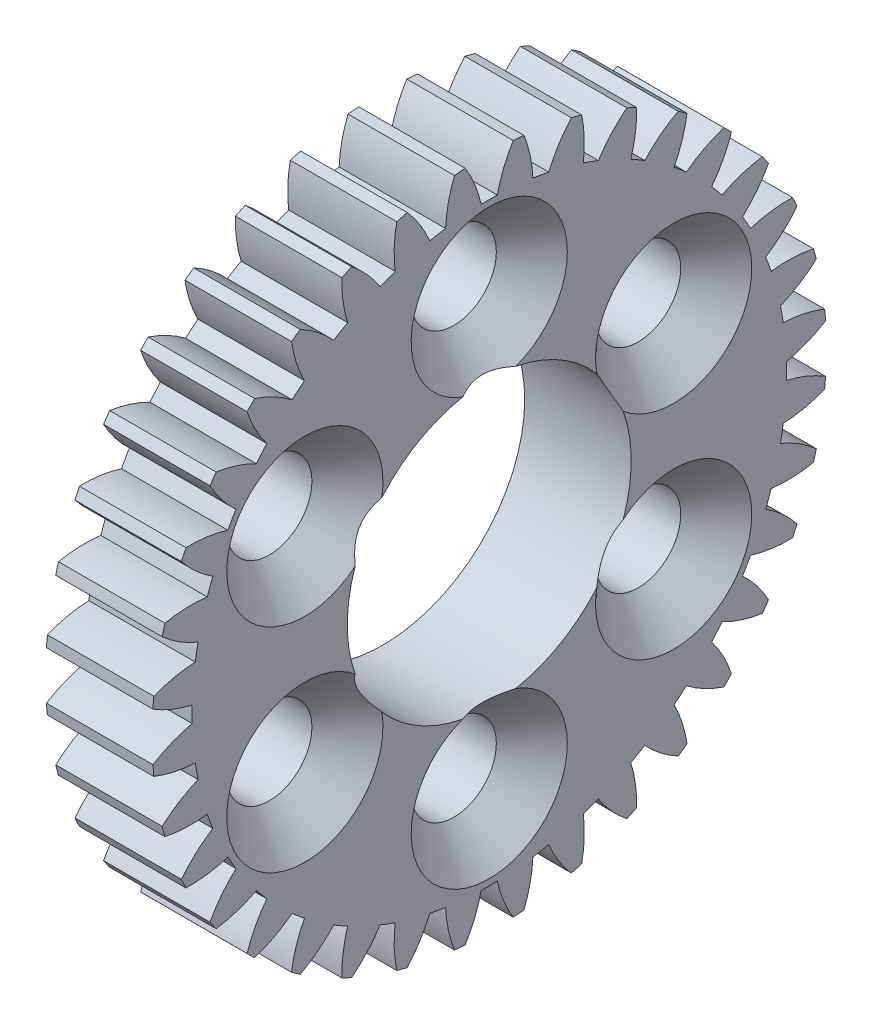
SolidWorks part; units mm, degrees
material "Náilon 101"
ref_plane "Plane1" through (0, 0, 0) normal (0, 0, 1) x (1, 0, 0)
ref_plane "Plane2" through (0, 0, 0) normal (0, 1, 0) x (1, 0, 0)
ref_plane "Plane3" through (0, 0, 0) normal (1, 0, 0) x (0, 0, -1)
sketch "HoldingSke" plane through (0, 0, 0) normal (0, 1, 0) x (1, 0, 0)
  line L0 (0, 0) -> (1.618, -1.1756)
  line L1 (-15, 0) -> (100, 0) construction
  line L2 (0, 0) -> (-2.1039, 2.3779)
  line L3 (0, 0) -> (-11.863, 4.5341)
  line L4 (0, 0) -> (6.9867, 5.0761)
  line L5 (0, 0) -> (-46.8476, -17.4728)
  line L6 (0, 0) -> (-2.4869, -1.6779)
  line L7 (-2.1039, 2.3779) -> (8.6586, 51.2059)
  line L8 (-76.2, 54.61) -> (-74.8, 54.61)
  line L9 (-71.009, 38.7566) -> (-53.1078, 45.2721)
  line L10 (-76.2, 71.12) -> (104.1128, 71.12)
  line L11 (0, 0) -> (-3, 0)
  line L12 (-76.2, 101.6) -> (-76.181, 101.6)
  line L13 (24.9733, 27.94) -> (52.9518, 28.4284)
  line L14 (24.9733, 27.94) -> (24.9743, 27.94)
  line L15 (24.9733, 27.94) -> (100.4006, 29.5858)
  line L16 (-63.627, -0.5) -> (-12.827, -0.5)
  circle A0 centre (0, 0) radius 4
  circle A1 centre (0, 0) radius 8.374
  circle A2 centre (0, 0) radius 37.5
  circle A3 centre (0, 0) radius 4
  dimension "Num_teeth" = 36
  dimension "Pitch_radius" = 180.3128
  dimension "Width" = 3
  dimension "Thickness" = 3
sketch "BasProSke" plane through (0, 0, 0) normal (0, 1, 0) x (1, 0, 0)
  line L0 (-10, 0) -> (60, 0) construction
  line L1 (0, 0) -> (0, 9.5)
  line L2 (0, 0) -> (3, 0)
  line L3 (3, 0) -> (3, 9.5)
  line L4 (3, 9.5) -> (0, 9.5)
  dimension "Thickness" = 3
  dimension "Diameter" = 19
revolve "Base-Revolve" add sketch "BasProSke" angle 360 about L0
sketch "TooCutSke" plane through (0, 0, 0) normal (1, 0, 0) x (0, 0, -1)
  line L1 (0, 0) -> (0, 107) construction
  line L2 (0, 0) -> (-0.4258, 8.9899) construction
  line L3 (0, 0) -> (-1.5676, 17.9172) construction
  line L4 (-0.4258, 8.9899) -> (-0.7838, 8.9586) construction
  arc A0 (0.2272, 8.3709) -> (-0.2272, 8.3709) centre (0, 0) ccw
  arc A1 (0.6921, 9.5002) -> (-0.6921, 9.5002) centre (0, 0) ccw
  circle A2 centre (0, 0) radius 9 construction
  circle A3 centre (0, 0) radius 8.4572 construction
  arc A4 (-0.2272, 8.3709) -> (-0.6921, 9.5002) centre (-3.7404, 7.5851) ccw
  arc A5 (0.6921, 9.5002) -> (0.2272, 8.3709) centre (3.7404, 7.5851) ccw
extrude "ToothCut" cut sketch "TooCutSke" along normal through all
fillet "Breaks" [suppressed] radius 0.01 tangent propagation no
fillet "RootFillets" [suppressed] radius 0.126
pattern_circular "TeethCuts" count 36 every 10 about axis through (-10, 0, 0) along (1, 0, 0) of "ToothCut", "RootFillets", "Breaks"
sketch "HubNeaOneSke" plane through (0, 0, 0) normal (-1, 0, 0) x (0, 0, 1)
  circle A0 centre (0, 0) radius 8.374
  dimension "Diameter" = 16.748
extrude "HubNearOne" [suppressed] add sketch "HubNeaOneSke" along normal blind 47.0001
sketch "HubNeaBotSke" plane through (0, 0, 0) normal (-1, 0, 0) x (0, 0, 1)
  circle A0 centre (0, 0) radius 8.374
  dimension "Diameter" = 16.748
extrude "HubNearBoth" [suppressed] add sketch "HubNeaBotSke" along normal blind 23.5
ref_plane "FarPln" through (3, 0, 0) normal (1, 0, 0) x (0, 0, -1)
sketch "HubFarSke" plane through (3, 0, 0) normal (1, 0, 0) x (0, 0, -1)
  circle A0 centre (0, 0) radius 8.374
  dimension "Diameter" = 16.748
extrude "HubFar" [suppressed] add sketch "HubFarSke" along normal blind 23.5
sketch "BorSke" plane through (0, 0, 0) normal (1, 0, 0) x (0, 0, -1)
  circle A0 centre (0, 0) radius 4
  dimension "Diameter" = 8
extrude "Bore" cut sketch "BorSke" along normal mid plane 100.0001
sketch "KeySke" plane through (0, 0, 0) normal (1, 0, 0) x (0, 0, -1)
  line L0 (-1.5, 0) -> (-1.5, 5.4)
  line L1 (-1.5, 5.4) -> (1.5, 5.4)
  line L2 (1.5, 5.4) -> (1.5, 0)
  line L3 (0, 0) -> (0, 34) construction
  line L4 (-1.5, 0) -> (1.5, 0)
  dimension "Width" = 3
extrude "Keyway" [suppressed] cut sketch "KeySke" along normal mid plane 100.0001
pattern_circular "Keyway2" [suppressed] count 2 every 90 about axis through (-10, 0, 0) along (1, 0, 0) reverse direction yes
sketch "Esboço1" plane through (3, 0, 0) normal (1, 0, 0) x (0, 0, -1)
  circle A0 centre (0, 0) radius 6 construction
  point P3 (0, 6)
  dimension "D1" = 12
hole_wizard "Escareado para parafuso com cabeça escareada chata de M21" positions "3DSketch2" profile "Esboço2" countersink size "M2" standard "ISO"
sketch3d "3DSketch2"
  point P0 (3, 6, 0)
sketch "Esboço2" plane through (3, 6, 0) normal (0, 1, 0) x (0, 0, -1)
  line L0 (0, 0) -> (0, 3.721)
  line L1 (0, 3.721) -> (1.2, 3)
  line L2 (1.2, 3) -> (1.2, 1)
  line L3 (1.2, 1) -> (2.2, 0)
  line L5 (2.2, 0) -> (0, 0)
  line L6 (-1.2, 1) -> (-2.2, 0) construction
  line L10 (0, 3.721) -> (-1.2, 3) construction
  line L11 (0, -6.35) -> (0, 107.95) construction
  dimension "Hole Dia." = 2.4
  dimension "Hole Depth" = 3
  dimension "Near C'Sink Dia." = 4.4
  dimension "Near C'Sink Angle" = 90
  dimension "Drill Angle" = 118
pattern_circular "PadrãoCircular1" count 6 over 360 about axis through (3, 0, 0) along (1, 0, 0) of "Escareado para parafuso com cabeça escareada chata de M21"
sketch "Esboço3" plane through (3, 0, 0) normal (1, 0, 0) x (0, 0, -1)
  line L0 (0, 0) -> (4, 0) construction
  line L1 (0, 0) -> (-4, 0) construction
  arc A0 (-3.031, -2.6102) -> (-0.7451, -3.93) centre (0, 0) ccw construction
  arc A1 (-0.7451, 3.93) -> (-3.031, 2.6102) centre (0, 0) ccw construction
equation "' \"Module@HoldingSke\" = 6.35"
equation "' \"Num_teeth@HoldingSke\" = 12"
equation "' \"Ap@HoldingSke\" =  20"
equation "' \"Ap@HoldingSke\" = 20"
equation "' \"Width@HoldingSke\" = 0.5 * 25.4"
equation "' \"Hub_dia@HoldingSke\"= 1 * 25.4"
equation "' \"Hub_dia@HoldingSke\" = 1 * 25.4"
equation "' \"Overall_len@HoldingSke\" = 1.0 * 25.4"
equation "' \"Bore@HoldingSke\" = 0.75 * 25.4"
equation "' \"T_dim@HoldingSke\" = 0.1 * 25.4"
equation "' \"Width@KeySke\" = 0.25 * 25.4"
equation "' \"Show_teeth@HoldingSke\" = 13"
equation "' \"Backlash@HoldingSke\" = 0.009 * 25.4"
equation "' \"Addendum_fac@HoldingSke\" = 1.0"
equation "' \"Dedendum_fac@HoldingSke\" = 1.25"
equation "' \"Dedendum_add@HoldingSke\" = 0.00005 * 25.4"
equation "' \"Clearance_fac@HoldingSke\" = 0.25"
equation "\"Pitch@HoldingSke\" = 1 / \"Module@HoldingSke\""
equation "\"Overcut_dia@TooCutSke\" = (\"Num_teeth@HoldingSke\" + 2 * \"Addendum_fac@HoldingSke\") / \"Pitch@HoldingSke\" + 0.002 * 25.4"
equation "\"Pitch_dia@TooCutSke\" = \"Num_teeth@HoldingSke\" / \"Pitch@HoldingSke\""
equation "\"Base_dia@TooCutSke\" = \"Num_teeth@HoldingSke\" / \"Pitch@HoldingSke\" * cos((\"Ap@HoldingSke\"  * 3.14159265 / 180))"
equation "\"Root_dia@TooCutSke\" = (\"Num_teeth@HoldingSke\" + 2) / \"Pitch@HoldingSke\" - 2 * (\"Addendum_fac@HoldingSke\" + \"Dedendum_fac@HoldingSke\") / \"Pitch@HoldingSke\" - \"Dedendum_add@HoldingSke\" * 2"
equation "\"Half_ang@TooCutSke\" = 180 / \"Num_teeth@HoldingSke\""
equation "\"Half_CT@TooCutSke\" = \"Num_teeth@HoldingSke\" / \"Pitch@HoldingSke\" * sin((3.14159265 / 2 / \"Num_teeth@HoldingSke\")) / 2 - 7 * \"Backlash@HoldingSke\" / 4"
equation "\"Flank_rad@TooCutSke\" = \"Num_teeth@HoldingSke\" / \"Pitch@HoldingSke\" / 5"
equation "\"Radius@RootFillets\" = \"Clearance_fac@HoldingSke\" / \"Pitch@HoldingSke\" + \"Dedendum_add@HoldingSke\""
equation "\"Break_rad@Breaks\" = 0.02 / \"Pitch@HoldingSke\""
equation "\"Thickness@HoldingSke\" = \"Width@HoldingSke\""
equation "\"OAL@HoldingSke\" = \"Thickness@HoldingSke\""
equation "\"MHD@HoldingSke\" = (\"Num_teeth@HoldingSke\" + 2) / \"Pitch@HoldingSke\" - 2 * (\"Addendum_fac@HoldingSke\" + \"Dedendum_fac@HoldingSke\")  / \"Pitch@HoldingSke\" - \"Dedendum_add@HoldingSke\" * 2"
equation "\"MBD@HoldingSke\" = (\"Num_teeth@HoldingSke\" + 2) / \"Pitch@HoldingSke\" - 2 * (\"Addendum_fac@HoldingSke\" + \"Dedendum_fac@HoldingSke\")  / \"Pitch@HoldingSke\" - \"Dedendum_add@HoldingSke\" * 2 - 0.002 * 25.4"
equation "\"MHD@HoldingSke\" = ((sgn( \"MHD@HoldingSke\" - \"Hub_dia@HoldingSke\" )-1)*( \"MHD@HoldingSke\" - \"Hub_dia@HoldingSke\" ))/-2+ \"Hub_dia@HoldingSke\""
equation "\"MBD@HoldingSke\" = ((sgn( \"MBD@HoldingSke\" - \"Bore@HoldingSke\" )-1)*( \"MBD@HoldingSke\" - \"Bore@HoldingSke\" ))/-2+ \"Bore@HoldingSke\""
equation "\"OAL@HoldingSke\" = ((sgn( \"OAL@HoldingSke\" - \"Overall_len@HoldingSke\" )+1)*( \"OAL@HoldingSke\" - \"Overall_len@HoldingSke\" ))/2 + \"Overall_len@HoldingSke\" + 0.000002 * 25.4"
equation "\"Num_teeth@TeethCuts\" = int( \"Show_teeth@HoldingSke\" ) + 1"
equation "\"Num_teeth@TeethCuts\" = ((sgn( \"Num_teeth@TeethCuts\" - \"Num_teeth@HoldingSke\" )-1)*( \"Num_teeth@TeethCuts\" - \"Num_teeth@HoldingSke\" ))/-2+ \"Num_teeth@HoldingSke\""
equation "\"Num_teeth@TeethCuts\" = ((sgn( \"Num_teeth@TeethCuts\" - 2.0)+1)*( \"Num_teeth@TeethCuts\" - 2.0))/2 +2.0"
equation "\"Angle@TeethCuts\" = 360.0 / \"Num_teeth@HoldingSke\""
equation "\"Diameter@BasProSke\" = (\"Num_teeth@HoldingSke\" + 2 * \"Addendum_fac@HoldingSke\") / \"Pitch@HoldingSke\""
equation "\"Thickness@BasProSke\"  = \"Thickness@HoldingSke\""
equation "' \"Fillet_rad@BasProSke\" =  \"Thickness@HoldingSke\" * 0.05"
equation "' \"Fillet_rad@BasProSke\" = \"Thickness@HoldingSke\" * 0.05"
equation "\"MHD@HoldingSke\" = ((sgn( \"MHD@HoldingSke\" - \"Root_dia@TooCutSke\" )-1)*( \"MHD@HoldingSke\" - \"Root_dia@TooCutSke\" ))/-2+ \"Root_dia@TooCutSke\""
equation "\"Diameter@HubNeaOneSke\" = \"MHD@HoldingSke\""
equation "\"Length@HubNearOne\" = \"OAL@HoldingSke\" - \"Thickness@BasProSke\""
equation "\"Diameter@HubNeaBotSke\" = \"MHD@HoldingSke\""
equation "\"Length@HubNearBoth\" = ( \"OAL@HoldingSke\" - \"Thickness@BasProSke\" ) / 2.0"
equation "\"Thickness@FarPln\" = \"Thickness@BasProSke\""
equation "\"Diameter@HubFarSke\" = \"MHD@HoldingSke\""
equation "\"Length@HubFar\" = ( \"OAL@HoldingSke\" - \"Thickness@BasProSke\" ) / 2.0"
equation "\"Diameter@BorSke\" = \"MBD@HoldingSke\""
equation "\"D1@Bore\" = \"OAL@HoldingSke\" * 2.0"
equation "\"D1@Keyway\" = \"OAL@HoldingSke\" * 2.0"
equation "\"Offset@KeySke\" = \"T_dim@HoldingSke\" + \"MBD@HoldingSke\" / 2.0"
